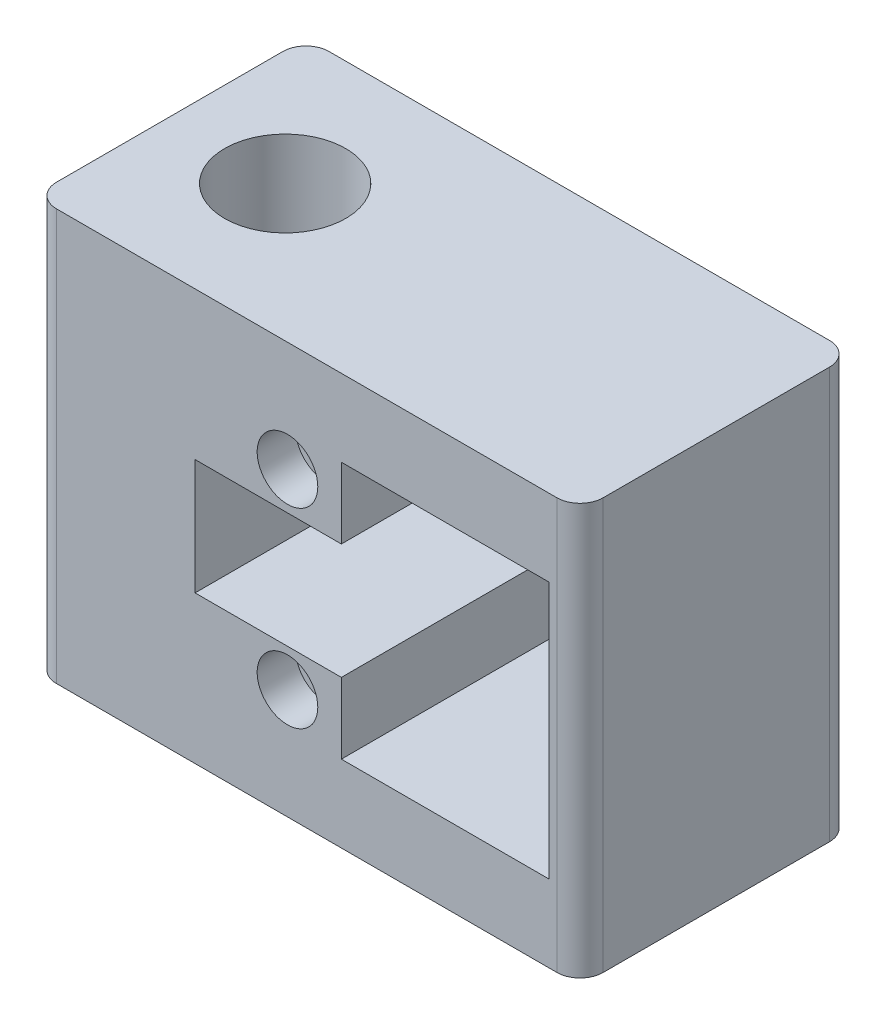
SolidWorks part; units mm, degrees
ref_plane "Front Plane" through (0, 0, 0) normal (0, 0, 1) x (1, 0, 0)
ref_plane "Top Plane" through (0, 0, 0) normal (0, 1, 0) x (1, 0, 0)
ref_plane "Right Plane" through (0, 0, 0) normal (1, 0, 0) x (0, 0, -1)
sketch "Sketch1" plane through (0, 0, 0) normal (0, 0, 1) x (1, 0, 0)
  line L0 (0, 30.734) -> (0, 42.418)
  line L1 (0, 0) -> (34.29, 0)
  line L2 (0, 0) -> (0, 11.684)
  line L3 (0, 42.418) -> (34.29, 42.418)
  line L4 (34.29, 0) -> (34.29, 42.418)
  line L5 (-50.8, 55.118) -> (39.37, 55.118)
  line L6 (-50.8, 55.118) -> (-50.8, -12.7)
  line L7 (-50.8, -12.7) -> (39.37, -12.7)
  line L8 (39.37, 55.118) -> (39.37, -12.7)
  line L9 (0, 30.734) -> (-24.13, 30.734)
  line L11 (0, 11.684) -> (-24.13, 11.684)
  line L12 (-24.13, 30.734) -> (-24.13, 11.684)
  dimension "D1" = 42.418
  dimension "D2" = 34.29
  dimension "D3" = 5.08
  dimension "D4" = 24.13
  dimension "D5" = 19.05
  dimension "D6" = 11.684
  dimension "D7" = 90.17
  dimension "D8" = 12.7
  dimension "D9" = 12.7
extrude "Boss-Extrude1" add sketch "Sketch1" along normal blind 42.418
sketch "Sketch2" plane through (0, 0, 0) normal (0, 0, -1) x (-1, 0, 0)
  line L1 (-39.37, 55.118) -> (50.8, 55.118)
  line L2 (-39.37, 55.118) -> (-39.37, -12.7)
  line L3 (-39.37, -12.7) -> (50.8, -12.7)
  line L4 (50.8, 55.118) -> (50.8, -12.7)
extrude "Boss-Extrude2" add sketch "Sketch2" along normal blind 2.54
sketch "Sketch3" plane through (0, -12.7, 0) normal (0, -1, 0) x (1, 0, 0)
  line L0 (-50.8, 42.418) -> (-50.8, -2.54) construction
  line L1 (-50.8, 42.418) -> (39.37, 42.418) construction
  circle A0 centre (-31.75, 19.939) radius 4.064
  dimension "D1" = 8.128
  dimension "D2" = 19.05
  dimension "D3" = 22.479
extrude "Cut-Extrude1" cut sketch "Sketch3" against normal through all
sketch "Sketch4" plane through (0, 0, 42.418) normal (0, 0, 1) x (1, 0, 0)
  line L2 (39.37, -12.7) -> (39.37, 55.118) construction
  line L4 (0, 30.734) -> (-24.13, 30.734) construction
  circle A0 centre (-8.89, 36.961) radius 5
  circle A1 centre (-8.89, 5.461) radius 5
  dimension "D1" = 10
  dimension "D2" = 10
  dimension "D3" = 31.5
  dimension "D4" = 6.227
  dimension "D5" = 48.26
  dimension "D6" = 48.26
extrude "Cut-Extrude2" cut sketch "Sketch4" against normal blind 6.35
sketch "Sketch5" plane through (0, 55.118, 0) normal (0, 1, 0) x (1, 0, 0)
  circle A0 centre (-31.75, -19.939) radius 9.9949
  dimension "D1" = 19.9898
extrude "Cut-Extrude3" cut sketch "Sketch5" against normal blind 15.24
fillet "Fillet1" radius 3.81 4 edges at (-50.8, 21.209, -2.54) (-50.8, 21.209, 42.418) (39.37, 21.209, -2.54) (39.37, 21.209, 42.418)
